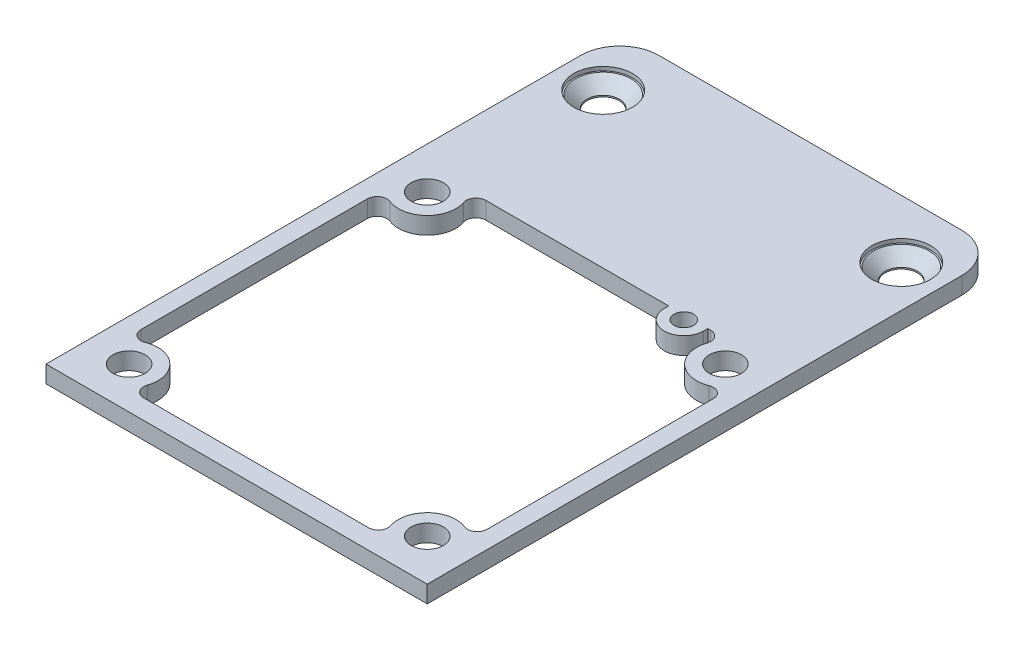
SolidWorks part; units mm, degrees
ref_plane "Front Plane" through (0, 0, 0) normal (0, 0, 1) x (1, 0, 0)
ref_plane "Top Plane" through (0, 0, 0) normal (0, 1, 0) x (1, 0, 0)
ref_plane "Right Plane" through (0, 0, 0) normal (1, 0, 0) x (0, 0, -1)
sketch "Sketch1" plane through (0, 0, 0) normal (0, 1, 0) x (1, 0, 0)
  line L0 (-15.5, 39.2) -> (15.5, 39.2)
  line L1 (-18.2, 15) -> (-18.2, -15) construction
  line L2 (17.7, -17.4996) -> (-17.7, -17.4996)
  line L3 (17.7, -17.4996) -> (17.7, 17.4996)
  line L4 (17.7, 17.4996) -> (-17.7, 17.4996)
  line L5 (-17.7, -17.4996) -> (-17.7, 17.4996)
  line L6 (17.7, -17.4996) -> (-17.7, 17.4996) construction
  line L7 (-19.5, 35.2) -> (-19.5, -19.5)
  line L8 (-19.5, -19.5) -> (19.5, -19.5)
  line L9 (19.5, -19.5) -> (19.5, 35.2)
  line L10 (17.7, 17.4996) -> (-17.7, -17.4996) construction
  line L11 (-15.25, 15.25) -> (-15.25, 17.9996) construction
  line L12 (11.2, 17.05) -> (11.2, 17.4996)
  line L13 (7.2, 17.05) -> (7.2, 17.4996)
  arc A0 (19.5, 35.2) -> (15.5, 39.2) centre (15.5, 35.2) ccw construction
  arc A1 (-15.5, 39.2) -> (-19.5, 35.2) centre (-15.5, 35.2) ccw construction
  arc A2 (19.5, 35.2) -> (15.5, 39.2) centre (15.5, 35.2) ccw
  arc A3 (-15.5, 39.2) -> (-19.5, 35.2) centre (-15.5, 35.2) ccw
  circle A4 centre (-15.25, -15.25) radius 1.65 construction
  circle A5 centre (15.25, -15.25) radius 1.65 construction
  circle A6 centre (-15.25, 15.25) radius 1.65 construction
  circle A7 centre (15.25, 15.25) radius 1.65 construction
  circle A8 centre (-15.25, 33.25) radius 1.65 construction
  circle A9 centre (15.25, 33.25) radius 1.65 construction
  circle A10 centre (-15.25, -15.25) radius 1.65
  circle A11 centre (15.25, -15.25) radius 1.65
  circle A12 centre (-15.25, 15.25) radius 1.65
  circle A13 centre (15.25, 15.25) radius 1.65
  circle A14 centre (-15.25, 33.25) radius 1.65
  circle A15 centre (15.25, 33.25) radius 1.65
  arc A16 (-15.2, 18) -> (-18.2, 15) centre (-15.2, 15) ccw construction
  circle A17 centre (-15.25, 15.25) radius 2.95
  circle A18 centre (15.25, 15.25) radius 2.95
  circle A19 centre (-15.25, -15.25) radius 2.95
  circle A20 centre (15.25, -15.25) radius 2.95
  circle A22 centre (9.2, 17.05) radius 2
  circle A23 centre (9.2, 17.05) radius 1
  circle A24 centre (9.2, 17.05) radius 0.9 construction
  point P29 (0, 0)
  dimension "D3" = 2
  dimension "D4" = 1
  dimension "D1" = 0.5
  dimension "D2" = 0.5
extrude "Base shape" add sketch "Sketch1" along normal blind 1.75 contours L0 A3 L7 L8 L9 A2 A20 L3 L2 A19 L5 A17 L4 A18 A15 A14 | A17 L4 L5 | L4 A17 L5 A12 | L5 A17 | L4 A17 | L3 A18 L4 A13 | L3 A18 | L4 A18 | L2 A19 L5 A10 | L2 A19 | L5 A19 | A19 L5 L2 | L2 A20 L3 A11 | L3 A20 | L2 A20 | A20 L2 L3 | A18 L3 L4 | A23 L4 A22 | A23 L4 A22 | A22 L4 L13 | A22 L12 L4 region at (-0.041, 0, -21.4203) region at (17.5279, 0, 17.307) region at (15.25, 0, 17.7828) region at (15.25, 0, 17.4246) region at (17.9015, 0, 15.25) region at (-15.25, 0, 17.7828) region at (-15.25, 0, 17.4246) region at (13.3348, 0, -13.1057) region at (17.9015, 0, -15.25) region at (-17.5279, 0, 17.307) region at (17.5279, 0, -17.307) region at (15.25, 0, -17.7828) region at (-17.9015, 0, 15.25) region at (11.1847, 0, -17.3875) region at (-17.9015, 0, -15.25) region at (-17.625, 0, -15.25) region at (11.1406, 0, -17.2709) region at (9.2, 0, -18.2243) region at (-17.5279, 0, -17.307) region at (7.2153, 0, -17.3875) region at (-15.25, 0, -17.7828)
fillet "Milling fillets" radius 1 8 edges at (-17.7, 0.875, 13.6068) (-13.3416, 0.875, 17.4996) (13.3416, 0.875, 17.4996) (17.7, 0.875, 13.6068) (17.7, 0.875, -13.6068) (13.3416, 0.875, -17.4996) (-13.3416, 0.875, -17.4996) (-17.7, 0.875, -13.6068)
sketch "Sketch3" plane through (0, 1.75, 0) normal (0, 1, 0) x (1, 0, 0)
  circle A0 centre (-15.25, 33.25) radius 3
  circle A1 centre (15.25, 33.25) radius 3
  dimension "D1" = 6
extrude "Screw head cut" cut sketch "Sketch3" against normal blind 0.4
chamfer "Screw head chamfer" distance 1.2 angle 45 2 edges at (15.25, 1.35, -31.6) (-15.25, 1.35, -31.6)
